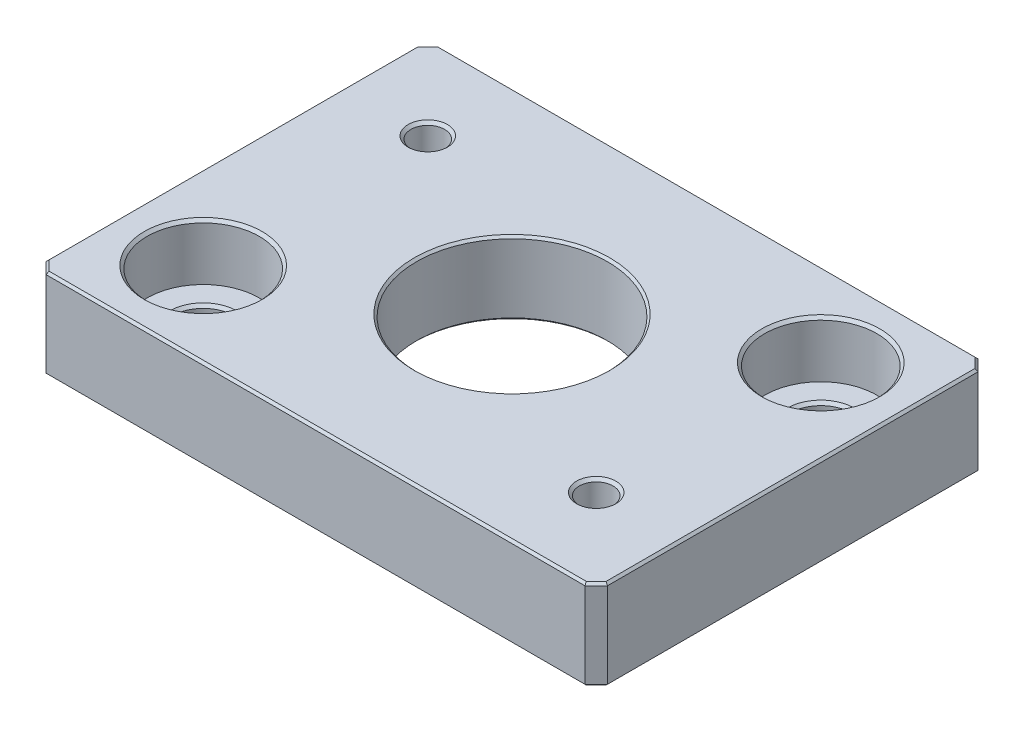
SolidWorks part; units mm, degrees
material "Plain Carbon Steel"
ref_plane "Front Plane" through (0, 0, 0) normal (0, 0, 1) x (1, 0, 0)
ref_plane "Top Plane" through (0, 0, 0) normal (0, 1, 0) x (1, 0, 0)
ref_plane "Right Plane" through (0, 0, 0) normal (1, 0, 0) x (0, 0, -1)
sketch "Sketch1" plane through (0, 0, 0) normal (0, 1, 0) x (1, 0, 0)
  line L1 (-17.5, -10) -> (17.5, -10) construction
  line L2 (-17.5, -10) -> (-17.5, 10) construction
  line L3 (-17.5, 10) -> (17.5, 10) construction
  line L4 (17.5, -10) -> (17.5, 10) construction
  line L5 (-17.5, -10) -> (17.5, 10) construction
  line L6 (-17.5, 10) -> (17.5, -10) construction
  line L7 (25, -17.5) -> (-25, -17.5)
  line L8 (25, -17.5) -> (25, 17.5)
  line L9 (25, 17.5) -> (-25, 17.5)
  line L10 (-25, -17.5) -> (-25, 17.5)
  line L11 (25, -17.5) -> (-25, 17.5) construction
  line L12 (25, 17.5) -> (-25, -17.5) construction
  circle A0 centre (-17.5, 10) radius 7.5 construction
  circle A1 centre (0, 0) radius 8.5
  point P0 (0, 0)
  point P6 (0, 0)
  dimension "D4" = 17
  dimension "D1" = 35
  dimension "D2" = 20
  dimension "D3" = 35
extrude "Boss-Extrude1" add sketch "Sketch1" along normal blind 8
hole_wizard "Ø3.0mm Dowel Hole1" positions "Sketch2" profile "Sketch3" hole size "Ø3.0" standard "ANSI Metric" end condition through all
sketch "Sketch2" plane through (0, 8, 0) normal (0, 1, 0) x (1, 0, 0)
  point P0 (-17.5, 10)
  point P3 (17.5, -10)
sketch "Sketch3" plane through (-17.5, 8, -10) normal (1, 0, 0) x (0, 0, 1)
  line L0 (0, 0) -> (0, 8)
  line L1 (0, 8) -> (1.75, 8)
  line L2 (1.5, 7.75) -> (1.5, 0.25)
  line L3 (1.5, 0.25) -> (1.75, 0)
  line L5 (1.75, 0) -> (0, 0)
  line L6 (-1.5, 0.25) -> (-1.75, 0) construction
  line L7 (1.75, 8) -> (1.5, 7.75)
  line L8 (-1.75, 8) -> (-1.5, 7.75) construction
  line L11 (0, -6.35) -> (0, 107.95) construction
  dimension "Thru Hole Dia." = 3
  dimension "Thru Hole Depth" = 8
  dimension "Near C'Sink Dia." = 3.5
  dimension "Near C'Sink Angle" = 90
  dimension "Far C'Sink Dia." = 3.5
  dimension "Far C'Sink Angle" = 90
hole_wizard "CBORE for M5 SHCS1" positions "Sketch4" profile "Sketch5" counterbore size "M5" standard "ANSI Metric" end condition through all
sketch "Sketch4" plane through (0, 8, 0) normal (0, 1, 0) x (1, 0, 0)
  point P0 (17.5, 10)
  point P3 (-17.5, -10)
sketch "Sketch5" plane through (17.5, 8, -10) normal (1, 0, 0) x (0, 0, 1)
  line L0 (0, 0) -> (0, 8)
  line L1 (2.75, 7.75) -> (3, 8)
  line L2 (2.75, 7.75) -> (2.75, 5.25)
  line L3 (2.75, 5.25) -> (3, 5)
  line L4 (3, 5) -> (5, 5)
  line L5 (5, 5) -> (5, 0.25)
  line L6 (5, 0.25) -> (5.25, 0)
  line L7 (5.25, 0) -> (0, 0)
  line L8 (-5, 0.25) -> (-5.25, 0) construction
  line L9 (-2.75, 5.25) -> (-3, 5) construction
  line L11 (0, -6.35) -> (0, 107.95) construction
  line L12 (3, 8) -> (0, 8)
  line L13 (-2.75, 7.75) -> (-3, 8) construction
  dimension "Thru Hole Dia." = 5.5
  dimension "Thru Hole Depth" = 8
  dimension "C'Bore Dia." = 10
  dimension "C'Bore Depth" = 5
  dimension "Near C'Sink Dia." = 10.5
  dimension "Near C'Sink Angle" = 90
  dimension "Mid C'Sink Dia." = 6
  dimension "Mid C'Sink Angle" = 90
  dimension "Far C'Sink Dia." = 6
  dimension "Far C'Sink Angle" = 90
sketch "Sketch6" plane through (0, 0, 0) normal (0, 1, 0) x (1, 0, 0)
  circle A0 centre (0, 0) radius 11.5
  circle A1 centre (0, 0) radius 8.5 construction
  dimension "D1" = 3
extrude "Cut-Extrude1" cut sketch "Sketch6" along normal blind 1.5
chamfer "Chamfer1" distance 1 4 edges at (25, 4, -17.5) (25, 4, 17.5) (-25, 4, -17.5) (-25, 4, 17.5)
chamfer "Chamfer2" distance 0.2 19 edges at (-24.5, 0, -17) (-25, 0, 0) (-24.5, 0, 17) (0, 0, 17.5) (24.5, 0, 17) (25, 0, 0) (24.5, 0, -17) (0, 0, -17.5) (0, 8, 8.5) (24.5, 8, 17) (0, 8, 17.5) (-24.5, 8, 17) (-25, 8, 0) (-24.5, 8, -17) (0, 8, -17.5) (24.5, 8, -17) (25, 8, 0) (0, 1.5, 8.5) (0, 0, 11.5)
